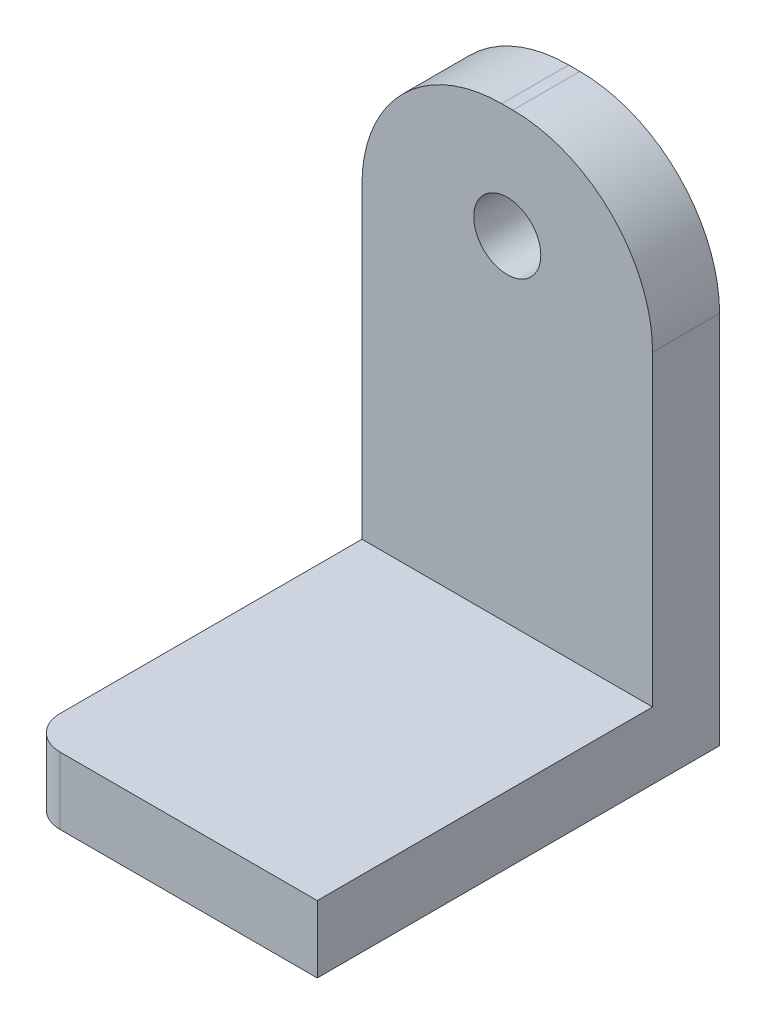
SolidWorks part; units mm, degrees
ref_plane "Front Plane" through (0, 0, 0) normal (0, 0, 1) x (1, 0, 0)
ref_plane "Top Plane" through (0, 0, 0) normal (0, 1, 0) x (1, 0, 0)
ref_plane "Right Plane" through (0, 0, 0) normal (1, 0, 0) x (0, 0, -1)
sketch "Sketch1" plane through (0, -44, 0) normal (0, 1, 0) x (1, 0, 0)
  line L0 (50.2641, 25) -> (50.2641, 28) construction
  line L1 (50.2641, -8) -> (50.2641, 28)
  line L2 (50.2641, -8) -> (27.2641, -8) construction
  line L3 (50.2641, -8) -> (27.2641, -8)
  line L4 (24.2641, -5) -> (24.2641, 25)
  line L5 (27.2641, 28) -> (50.2641, 28)
  arc A0 (27.2641, 28) -> (24.2641, 25) centre (27.2641, 25) ccw construction
  arc A1 (24.2641, -5) -> (27.2641, -8) centre (27.2641, -5) ccw construction
  arc A2 (27.2641, 28) -> (24.2641, 25) centre (27.2641, 25) ccw
  arc A3 (24.2641, -5) -> (27.2641, -8) centre (27.2641, -5) ccw
extrude "Boss-Extrude1" add sketch "Sketch1" along normal blind 6
sketch "Sketch2" plane through (0, -38, 0) normal (0, 1, 0) x (1, 0, 0)
  line L0 (24.2641, 25) -> (24.2641, -5) construction
  line L1 (50.2641, 28) -> (24.2641, 28)
  line L2 (50.2641, 28) -> (50.2641, 22)
  line L3 (50.2641, 22) -> (24.2641, 22)
  line L4 (24.2641, 28) -> (24.2641, 22)
  dimension "D1" = 6
extrude "Boss-Extrude2" add sketch "Sketch2" along normal blind 40
fillet "Fillet1" radius 12.5 2 edges at (24.2641, 2, -25) (50.2641, 2, -25)
sketch "Sketch3" plane through (0, 0, -22) normal (0, 0, 1) x (1, 0, 0)
  circle A0 centre (37.2641, -8) radius 3
extrude "Cut-Extrude1" cut sketch "Sketch3" against normal through all
